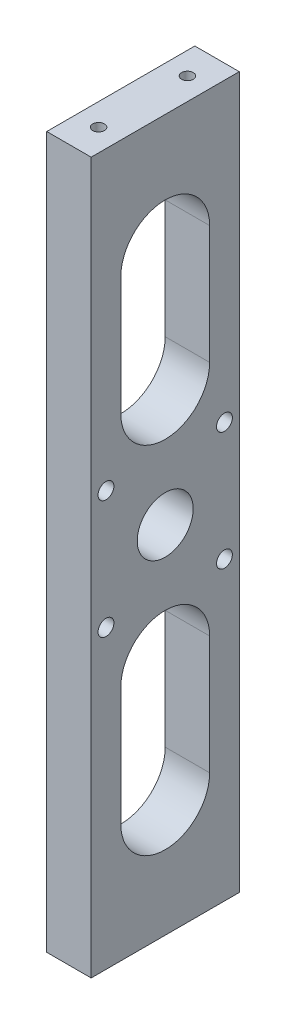
SolidWorks part; units mm, degrees
material "6061 Alloy"
ref_plane "Front Plane" through (0, 0, 0) normal (0, 0, 1) x (1, 0, 0)
ref_plane "Top Plane" through (0, 0, 0) normal (0, 1, 0) x (1, 0, 0)
ref_plane "Right Plane" through (0, 0, 0) normal (1, 0, 0) x (0, 0, -1)
sketch "Sketch1" plane through (0, 0, 0) normal (1, 0, 0) x (0, 0, -1)
  line L1 (-15.875, -76.2) -> (15.875, -76.2)
  line L2 (-15.875, -76.2) -> (-15.875, 76.2)
  line L3 (-15.875, 76.2) -> (15.875, 76.2)
  line L4 (15.875, -76.2) -> (15.875, 76.2)
  line L5 (-15.875, -76.2) -> (15.875, 76.2) construction
  line L6 (-15.875, 76.2) -> (15.875, -76.2) construction
  point P0 (0, 0)
  dimension "D1" = 31.75
  dimension "D2" = 152.4
extrude "Boss-Extrude1" add sketch "Sketch1" along normal mid plane 9.525
sketch "Sketch2" plane through (0, 76.2, 0) normal (0, 1, 0) x (1, 0, 0)
  line L0 (0, 9.525) -> (0, -9.525) construction
  line L1 (-4.7625, 15.875) -> (-4.7625, -15.875) construction
  line L2 (4.7625, 15.875) -> (-4.7625, 15.875) construction
  point P2 (0, 0)
  point P5 (-4.7625, 0)
  point P8 (0, 15.875)
  point P10 (0, 9.525)
  point P11 (0, -9.525)
  dimension "D1" = 19.05
hole_wizard "M3x0.5 Tapped Hole1" positions "Sketch3" profile "Sketch4" tap size "M3x0.5" standard "ANSI Metric"
sketch "Sketch3" plane through (0, 76.2, 0) normal (0, 1, 0) x (1, 0, 0)
  point P0 (0, 9.525)
  point P3 (0, -9.525)
sketch "Sketch4" plane through (0, 76.2, -9.525) normal (1, 0, 0) x (0, 0, 1)
  line L0 (0, 0) -> (0, 13.4511)
  line L1 (0, 13.4511) -> (1.25, 12.7)
  line L2 (1.25, 12.7) -> (1.25, 0)
  line L5 (1.25, 0) -> (0, 0)
  line L10 (0, 13.4511) -> (-1.25, 12.7) construction
  line L11 (0, -6.35) -> (0, 107.95) construction
  dimension "Tap Drill Dia." = 2.5
  dimension "Tap Drill Depth" = 12.7
  dimension "Drill Angle" = 118
cosmetic thread "Hole Thread1" parameters "D1"=6.096, "D2"=3
cosmetic thread "Hole Thread2" parameters "D1"=6.096, "D2"=3
mirror "Mirror1" about plane through (0, 0, 0) normal (0, 1, 0) of "M3x0.5 Tapped Hole1"
cosmetic thread "Hole Thread3" parameters "D1"=6.096, "D2"=3
cosmetic thread "Hole Thread4" parameters "D1"=6.096, "D2"=3
sketch "Sketch5" plane through (4.7625, 0, 0) normal (1, 0, 0) x (0, 0, -1)
  point P0 (0, 0)
hole_wizard "Ø12.0mm Dowel Hole1" positions "Sketch6" profile "Sketch8" hole size "Ø12.0" standard "ANSI Metric" end condition through all
sketch "Sketch6" plane through (4.7625, 0, 0) normal (1, 0, 0) x (0, 0, -1)
  point P0 (0, 0)
sketch "Sketch8" plane through (4.7625, 0, 0) normal (0, 1, 0) x (0, 0, -1)
  line L0 (0, 0) -> (0, 9.525)
  line L1 (0, 9.525) -> (6, 9.525)
  line L2 (6, 9.525) -> (6, 0)
  line L5 (6, 0) -> (0, 0)
  line L11 (0, -6.35) -> (0, 107.95) construction
  dimension "Thru Hole Dia." = 12
  dimension "Thru Hole Depth" = 9.525
sketch "Sketch9" plane through (4.7625, 0, 0) normal (1, 0, 0) x (0, 0, -1)
  line L0 (0, 50.8) -> (0, 25.4) construction
  line L1 (0, 55) -> (0, -55) construction
  line L2 (9.525, 50.8) -> (9.525, 25.4)
  line L3 (-9.525, 50.8) -> (-9.525, 25.4)
  line L4 (0, -25.4) -> (0, -50.8) construction
  line L5 (9.525, -25.4) -> (9.525, -50.8)
  line L6 (-9.525, -25.4) -> (-9.525, -50.8)
  line L7 (0, 25.4) -> (0, -25.4)
  line L8 (55, 0) -> (-55, 0) construction
  arc A0 (9.525, 50.8) -> (-9.525, 50.8) centre (0, 50.8) ccw
  arc A1 (-9.525, 25.4) -> (9.525, 25.4) centre (0, 25.4) ccw
  arc A2 (9.525, -25.4) -> (-9.525, -25.4) centre (0, -25.4) ccw
  arc A3 (-9.525, -50.8) -> (9.525, -50.8) centre (0, -50.8) ccw
  point P5 (0, 38.1)
  point P10 (0, -38.1)
  point P19 (0, 0)
  dimension "D1" = 25.4
  dimension "D2" = 19.05
  dimension "D3" = 25.4
extrude "Cut-Extrude1" cut sketch "Sketch9" against normal through all contours L6 A3 L5 A2 | L3 A1 L2 A0 region at (4.7625, -38.1, 0) region at (4.7625, 38.1, 0)
sketch "Sketch11" plane through (-4.7625, 0, 0) normal (-1, 0, 0) x (0, 0, 1)
  line L0 (15.875, 76.2) -> (15.875, -76.2) construction
  line L1 (-12.7, -12.7) -> (12.7, -12.7)
  line L2 (-12.7, -12.7) -> (-12.7, 12.7)
  line L3 (-12.7, 12.7) -> (12.7, 12.7)
  line L4 (12.7, -12.7) -> (12.7, 12.7)
  line L5 (-12.7, -12.7) -> (12.7, 12.7) construction
  line L6 (-12.7, 12.7) -> (12.7, -12.7) construction
  arc A0 (-9.525, 25.4) -> (9.525, 25.4) centre (0, 25.4) ccw construction
  arc A1 (9.525, -25.4) -> (-9.525, -25.4) centre (0, -25.4) ccw construction
  point P0 (0, 0)
  point P9 (0, 15.875)
  point P10 (0, -15.875)
  dimension "D1" = 3.175
  dimension "D2" = 3.175
hole_wizard "M3 Clearance Hole1" positions "Sketch12" profile "Sketch14" hole size "M3" standard "ANSI Metric"
sketch "Sketch12" plane through (-4.7625, 0, 0) normal (-1, 0, 0) x (0, 0, 1)
  point P0 (-12.7, 12.7)
  point P3 (12.7, 12.7)
  point P6 (12.7, -12.7)
  point P9 (-12.7, -12.7)
sketch "Sketch14" plane through (-4.7625, 12.7, -12.7) normal (0, 1, 0) x (0, 0, 1)
  line L0 (0, 0) -> (0, 16.2615)
  line L1 (0, 16.2615) -> (1.7, 15.24)
  line L2 (1.7, 15.24) -> (1.7, 0)
  line L5 (1.7, 0) -> (0, 0)
  line L10 (0, 16.2615) -> (-1.7, 15.24) construction
  line L11 (0, -6.35) -> (0, 107.95) construction
  dimension "Hole Dia." = 3.4
  dimension "Hole Depth" = 15.24
  dimension "Drill Angle" = 118
